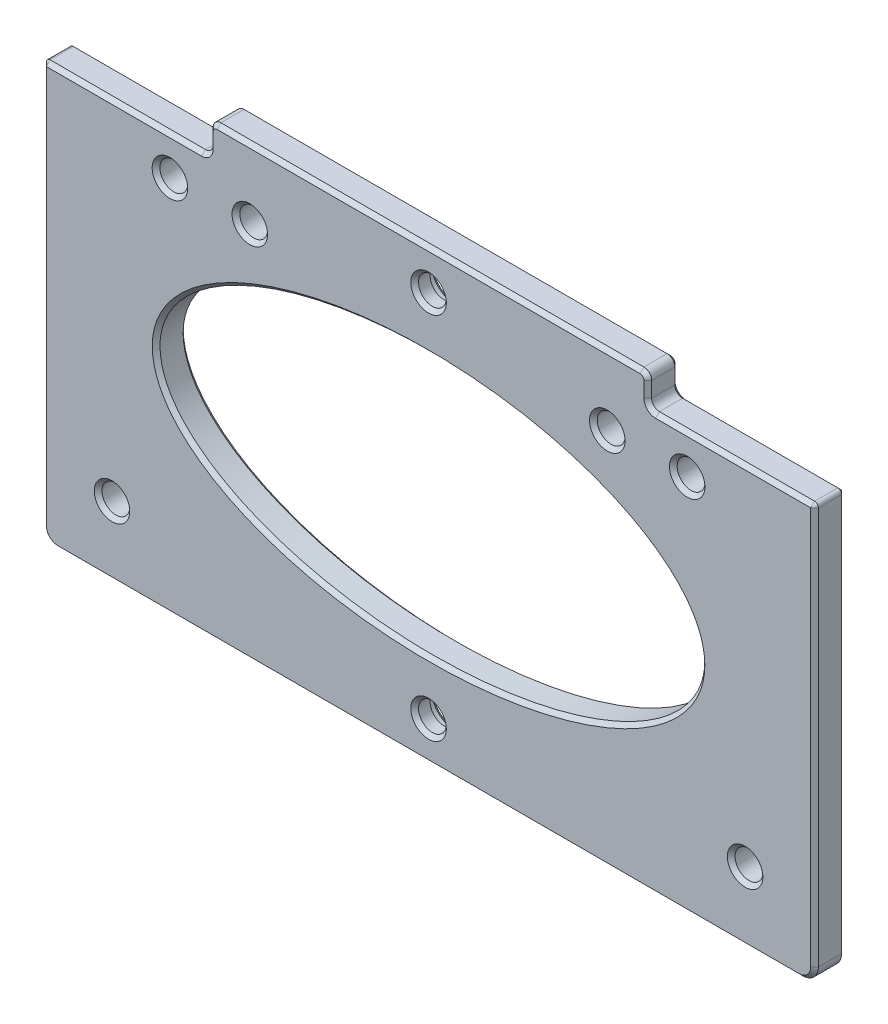
SolidWorks part; units mm, degrees
ref_plane "Front" through (0, 0, 0) normal (0, 0, 1) x (1, 0, 0)
ref_plane "Top" through (0, 0, 0) normal (0, 1, 0) x (1, 0, 0)
ref_plane "Right" through (0, 0, 0) normal (1, 0, 0) x (0, 0, -1)
sketch "Skizze1" plane through (0, 0, 0) normal (0, 0, 1) x (1, 0, 0)
  line L0 (0, 0) -> (0, -31.9464) construction
  line L5 (50, -29) -> (-50, -29)
  line L6 (-50, -29) -> (-50, 25)
  line L7 (-50, 25) -> (-28.4, 25)
  line L9 (0, 0) -> (-55.464, 0) construction
  line L10 (50, 25) -> (28.4, 25)
  line L11 (50, -29) -> (50, 25)
  line L12 (28.4, 25) -> (28.4, 29)
  line L13 (28.9, 28.5) -> (28.9, 25.5) construction
  line L14 (28.4, 29) -> (-28.4, 29)
  line L15 (-28.4, 25) -> (-28.4, 29)
  line L18 (-28.4, 25) -> (0, 25) construction
  line L19 (28.4, 25) -> (0, 25) construction
  point P0 (0, 0)
  point P12 (0, -29)
  point P21 (0, 29)
  point P25 (28.9, 27)
  dimension "D1" = 100
  dimension "D2" = 29
  dimension "D3" = 25
  dimension "D4" = 4
  dimension "D5" = 0.5
extrude "Aufsatz-Linear austragen1" add sketch "Skizze1" along normal blind 4
sketch "Skizze2" plane through (0, 0, 4) normal (0, 0, 1) x (1, 0, 0)
  circle A0 centre (0, 23.8979) radius 1.8
  circle A1 centre (0, -23.8979) radius 1.8
  dimension "D1" = 3.6
extrude "Schnitt-Linear austragen1" cut sketch "Skizze2" against normal blind 10
sketch "Skizze3" plane through (0, 0, 0) normal (0, 0, -1) x (-1, 0, 0)
  circle A0 centre (0, -23.8979) radius 3.15
  arc A2 (3.15, 23.8979) -> (-3.15, 23.8979) centre (0, 23.8979) ccw construction
  circle A3 centre (0, 23.8979) radius 3.15
  dimension "D1" = 6.3
  dimension "D2" = 6.3
extrude "Schnitt-Linear austragen2" cut sketch "Skizze3" against normal blind 2
sketch "Skizze4" plane through (0, 0, 4) normal (0, 0, 1) x (1, 0, 0)
  circle A0 centre (-33.5, 20) radius 1.8
  circle A1 centre (33.5, 20) radius 1.8
  circle A2 centre (-41, -20) radius 1.8
  circle A3 centre (41, -20) radius 1.8
  circle A4 centre (-23.15, 20) radius 1.8
  circle A5 centre (23.15, 20) radius 1.8
  dimension "D1" = 3.6
extrude "Schnitt-Linear austragen3" cut sketch "Skizze4" against normal blind 10
sketch "Skizze5" plane through (0, 0, 0) normal (0, 0, -1) x (-1, 0, 0)
  ellipse E0 centre (0, 0) end of major axis (35.2853, 0) minor radius 16.9659
extrude "Schnitt-Linear austragen4" cut sketch "Skizze5" against normal blind 10
fillet "Verrundung1" radius 1 4 edges at (-28.4, 25, 2) (-28.4, 29, 2) (28.4, 25, 2) (28.4, 29, 2)
fillet "Verrundung2" radius 0.5 2 edges at (-50, 25, 2) (50, 25, 2)
fillet "Verrundung3" radius 2 2 edges at (-50, -29, 2) (50, -29, 2)
chamfer "Fase1" distance 0.5 angle 45 50 edges at (-28.6929, 25.2929, 4) (-28.4, 27, 4) (-28.1071, 28.7071, 4) (0, 29, 4) (28.1071, 28.7071, 4) (28.4, 27, 4) (28.6929, 25.2929, 4) (39.45, 25, 4) (49.8536, 24.8536, 4) (50, -1.25, 4) (0, -29, 4) (-50, -1.25, 4) (-49.8536, 24.8536, 4) (-39.45, 25, 4) (1.8, -23.8979, 4) (1.8, 23.8979, 4) (-31.7, 20, 4) (35.3, 20, 4) (-39.2, -20, 4) (42.8, -20, 4) (0, -29, 0) (50, -1.25, 0) (49.8536, 24.8536, 0) (39.45, 25, 0) (28.6929, 25.2929, 0) (28.4, 27, 0) (28.1071, 28.7071, 0) (0, 29, 0) (-28.1071, 28.7071, 0) (-28.4, 27, 0) (-28.6929, 25.2929, 0) (-39.45, 25, 0) (-49.8536, 24.8536, 0) (-50, -1.25, 0) (-3.15, -23.8979, 0) (-35.3, 20, 0) (31.7, 20, 0) (-42.8, -20, 0) (39.2, -20, 0) (-35.2853, 0, 4) (-35.2853, 0, 0) (-3.15, 23.8979, 0) (24.95, 20, 4) (-21.35, 20, 4) (21.35, 20, 0) (-24.95, 20, 0) (49.4142, -28.4142, 4) (-49.4142, -28.4142, 4) (49.4142, -28.4142, 0) (-49.4142, -28.4142, 0)
